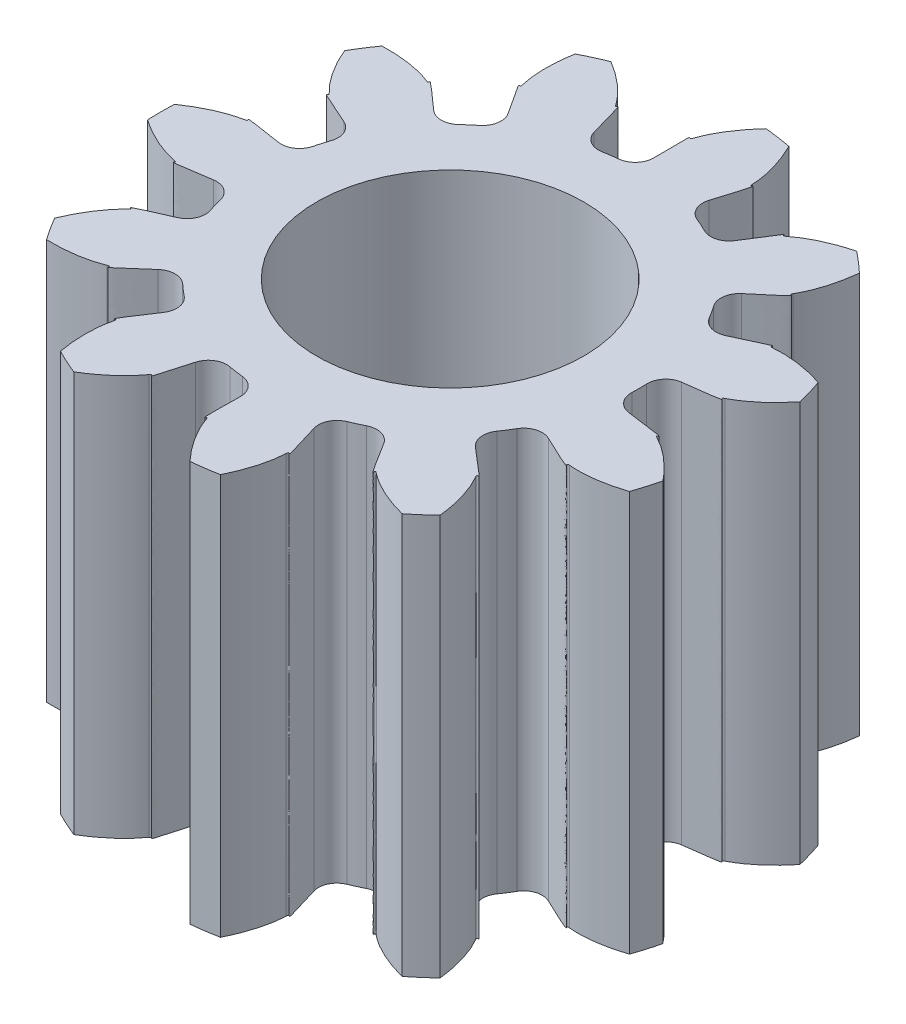
SolidWorks part; units mm, degrees
ref_plane "Front" through (0, 0, 0) normal (0, 0, 1) x (1, 0, 0)
ref_plane "Top" through (0, 0, 0) normal (0, 1, 0) x (1, 0, 0)
ref_plane "Right" through (0, 0, 0) normal (1, 0, 0) x (0, 0, -1)
ref_plane "Plane1" through (0, -4.5, 0) normal (0, -1, 0) x (1, 0, 0)
sketch "Sketch1" plane through (0, -4.5, 0) normal (0, -1, 0) x (1, 0, 0)
  line L0 (-2.1271, 0.9333) -> (-1.9459, 0.8539)
  line L1 (-2.0986, 0.3337) -> (-2.294, 0.3649)
  line L2 (-2.294, -0.3649) -> (-2.0986, -0.3337)
  line L3 (-1.9459, -0.8539) -> (-2.1271, -0.9333)
  line L4 (-1.7326, -1.5472) -> (-1.585, -1.4154)
  line L5 (-1.1754, -1.7703) -> (-1.2849, -1.9352)
  line L6 (-0.6211, -2.2383) -> (-0.5682, -2.0476)
  line L7 (-0.0317, -2.1248) -> (-0.0347, -2.3226)
  line L8 (0.6877, -2.2188) -> (0.629, -2.0298)
  line L9 (1.1221, -1.8046) -> (1.2265, -1.9727)
  line L10 (1.778, -1.4948) -> (1.6265, -1.3675)
  line L11 (1.9196, -0.9115) -> (2.0983, -0.9964)
  line L12 (2.3039, -0.2962) -> (2.1076, -0.271)
  line L13 (2.1076, 0.271) -> (2.3039, 0.2962)
  line L14 (2.0983, 0.9964) -> (1.9196, 0.9115)
  line L15 (1.6265, 1.3675) -> (1.778, 1.4948)
  line L16 (1.2265, 1.9727) -> (1.1221, 1.8046)
  line L17 (0.629, 2.0298) -> (0.6877, 2.2188)
  line L18 (-0.0347, 2.3226) -> (-0.0317, 2.1248)
  line L19 (-0.5682, 2.0476) -> (-0.6211, 2.2383)
  line L20 (-1.2849, 1.9352) -> (-1.1754, 1.7703)
  line L21 (-1.585, 1.4154) -> (-1.7326, 1.5472)
  arc A0 (-1.9459, 0.8539) -> (-2.0986, 0.3337) centre (0, 0) ccw
  arc A1 (-3.2465, 0.1513) -> (-3.2465, -0.1513) centre (0, 0) ccw
  arc A2 (-2.0986, -0.3337) -> (-1.9459, -0.8539) centre (0, 0) ccw
  arc A3 (-2.8129, -1.6279) -> (-2.6493, -1.8825) centre (0, 0) ccw
  arc A4 (-1.585, -1.4154) -> (-1.1754, -1.7703) centre (0, 0) ccw
  arc A5 (-1.4863, -2.8902) -> (-1.211, -3.016) centre (0, 0) ccw
  arc A6 (-0.5682, -2.0476) -> (-0.0317, -2.1248) centre (0, 0) ccw
  arc A7 (0.3122, -3.235) -> (0.6118, -3.1919) centre (0, 0) ccw
  arc A8 (0.629, -2.0298) -> (1.1221, -1.8046) centre (0, 0) ccw
  arc A9 (2.0116, -2.5526) -> (2.2404, -2.3544) centre (0, 0) ccw
  arc A10 (1.6265, -1.3675) -> (1.9196, -0.9115) centre (0, 0) ccw
  arc A11 (3.0723, -1.0598) -> (3.1576, -0.7694) centre (0, 0) ccw
  arc A12 (2.1076, -0.271) -> (2.1076, 0.271) centre (0, 0) ccw
  arc A13 (3.1576, 0.7694) -> (3.0723, 1.0598) centre (0, 0) ccw
  arc A14 (1.9196, 0.9115) -> (1.6265, 1.3675) centre (0, 0) ccw
  arc A15 (2.2404, 2.3544) -> (2.0116, 2.5526) centre (0, 0) ccw
  arc A16 (1.1221, 1.8046) -> (0.629, 2.0298) centre (0, 0) ccw
  arc A17 (0.6118, 3.1919) -> (0.3122, 3.235) centre (0, 0) ccw
  arc A18 (-0.0317, 2.1248) -> (-0.5682, 2.0476) centre (0, 0) ccw
  arc A19 (-1.211, 3.016) -> (-1.4863, 2.8902) centre (0, 0) ccw
  arc A20 (-1.1754, 1.7703) -> (-1.585, 1.4154) centre (0, 0) ccw
  arc A21 (-2.6493, 1.8825) -> (-2.8129, 1.6279) centre (0, 0) ccw
  ellipse E0 centre (-3.0578, -0.4226) end of major axis (-2.2508, 0.2924) minor radius 0.5689 (-2.7016, 0.3954) -> (-3.2465, 0.1513) ccw
  ellipse E1 centre (-3.0578, 0.4226) end of major axis (-2.2508, -0.2924) minor radius 0.5689 (-3.2465, -0.1513) -> (-2.7016, -0.3954) ccw
  ellipse E2 centre (-2.3439, -2.0087) end of major axis (-2.6362, -3.0465) minor radius 0.5689 (-2.4865, -1.128) -> (-2.8129, -1.6279) ccw
  ellipse E3 centre (-2.8009, -1.2977) end of major axis (-1.7354, -1.4629) minor radius 0.5689 (-2.6493, -1.8825) -> (-2.059, -1.7932) ccw
  ellipse E4 centre (-0.8858, -2.957) end of major axis (-1.201, -1.9259) minor radius 0.5689 (-1.482, -2.2932) -> (-1.4863, -2.8902) ccw
  ellipse E5 centre (-1.6547, -2.6059) end of major axis (-2.6404, -3.043) minor radius 0.5689 (-1.211, -3.016) -> (-0.7626, -2.6217) ccw
  ellipse E6 centre (0.8535, -2.9665) end of major axis (0.0309, -2.2695) minor radius 0.5689 (-0.0069, -2.7304) -> (0.3122, -3.235) ccw
  ellipse E7 centre (0.0169, -3.0868) end of major axis (-0.5761, -3.9874) minor radius 0.5689 (0.6118, -3.1919) -> (0.7758, -2.6178) ccw
  ellipse E8 centre (2.3218, -2.0342) end of major axis (3.3907, -2.1758) minor radius 0.5689 (1.4704, -2.3007) -> (2.0116, -2.5526) ccw
  ellipse E9 centre (1.6831, -2.5877) end of major axis (1.695, -1.5095) minor radius 0.5689 (2.2404, -2.3544) -> (2.068, -1.7828) ccw
  ellipse E10 centre (3.053, -0.456) end of major axis (4.0288, 0.0027) minor radius 0.5689 (2.4808, -1.1405) -> (3.0723, -1.0598) ccw
  ellipse E11 centre (2.8149, -1.267) end of major axis (2.242, -0.3535) minor radius 0.5689 (3.1576, -0.7694) -> (2.7036, -0.3818) ccw
  ellipse E12 centre (2.8149, 1.267) end of major axis (2.242, 0.3535) minor radius 0.5689 (2.7036, 0.3818) -> (3.1576, 0.7694) ccw
  ellipse E13 centre (3.053, 0.456) end of major axis (4.0288, -0.0027) minor radius 0.5689 (3.0723, 1.0598) -> (2.4808, 1.1405) ccw
  ellipse E14 centre (1.6831, 2.5877) end of major axis (1.695, 1.5095) minor radius 0.5689 (2.068, 1.7828) -> (2.2404, 2.3544) ccw
  ellipse E15 centre (2.3218, 2.0342) end of major axis (3.3907, 2.1758) minor radius 0.5689 (2.0116, 2.5526) -> (1.4704, 2.3007) ccw
  ellipse E16 centre (0.0169, 3.0868) end of major axis (0.6098, 2.1863) minor radius 0.5689 (0.7758, 2.6178) -> (0.6118, 3.1919) ccw
  ellipse E17 centre (0.8535, 2.9665) end of major axis (1.6761, 3.6636) minor radius 0.5689 (0.3122, 3.235) -> (-0.0069, 2.7304) ccw
  ellipse E18 centre (-1.6547, 2.6059) end of major axis (-0.669, 2.1689) minor radius 0.5689 (-0.7626, 2.6217) -> (-1.211, 3.016) ccw
  ellipse E19 centre (-0.8858, 2.957) end of major axis (-0.5707, 3.9882) minor radius 0.5689 (-1.4863, 2.8902) -> (-1.482, 2.2932) ccw
  ellipse E20 centre (-2.8009, 1.2977) end of major axis (-1.7354, 1.4629) minor radius 0.5689 (-2.059, 1.7932) -> (-2.6493, 1.8825) ccw
  ellipse E21 centre (-2.3439, 2.0087) end of major axis (-2.6362, 3.0465) minor radius 0.5689 (-2.8129, 1.6279) -> (-2.4865, 1.128) ccw
  spline S0 degree 3 poles (-2.294, 0.3649) (-2.8728, 0.4571) (-2.6163, 0.4112) (-2.7016, 0.3954) knots 0 0 0 0 1 1 1 1
  spline S1 degree 3 poles (-2.294, -0.3649) (-2.8728, -0.4571) (-2.6163, -0.4112) (-2.7016, -0.3954) knots 0 0 0 0 1 1 1 1
  spline S2 degree 3 poles (-2.1271, -0.9333) (-2.6639, -1.1686) (-2.4233, -1.0686) (-2.4865, -1.128) knots 0 0 0 0 1 1 1 1
  spline S3 degree 3 poles (-1.7326, -1.5472) (-2.1696, -1.9377) (-1.9787, -1.7604) (-2.059, -1.7932) knots 0 0 0 0 1 1 1 1
  spline S4 degree 3 poles (-1.2849, -1.9352) (-1.6093, -2.4233) (-1.4609, -2.2091) (-1.482, -2.2932) knots 0 0 0 0 1 1 1 1
  spline S5 degree 3 poles (-0.6211, -2.2383) (-0.7776, -2.8031) (-0.7128, -2.5507) (-0.7626, -2.6217) knots 0 0 0 0 1 1 1 1
  spline S6 degree 3 poles (-0.0347, -2.3226) (-0.0437, -2.9086) (-0.0347, -2.6482) (-0.0069, -2.7304) knots 0 0 0 0 1 1 1 1
  spline S7 degree 3 poles (0.6877, -2.2188) (0.8613, -2.7785) (0.7794, -2.5312) (0.7758, -2.6178) knots 0 0 0 0 1 1 1 1
  spline S8 degree 3 poles (1.2265, -1.9727) (1.5358, -2.4705) (1.4026, -2.2466) (1.4704, -2.3007) knots 0 0 0 0 1 1 1 1
  spline S9 degree 3 poles (1.778, -1.4948) (2.2268, -1.8718) (2.0241, -1.708) (2.068, -1.7828) knots 0 0 0 0 1 1 1 1
  spline S10 degree 3 poles (2.0983, -0.9964) (2.6277, -1.248) (2.3945, -1.1317) (2.4808, -1.1405) knots 0 0 0 0 1 1 1 1
  spline S11 degree 3 poles (2.3039, -0.2962) (2.8853, -0.3707) (2.6262, -0.3425) (2.7036, -0.3818) knots 0 0 0 0 1 1 1 1
  spline S12 degree 3 poles (2.3039, 0.2962) (2.8853, 0.3707) (2.6262, 0.3425) (2.7036, 0.3818) knots 0 0 0 0 1 1 1 1
  spline S13 degree 3 poles (2.0983, 0.9964) (2.6277, 1.248) (2.3945, 1.1317) (2.4808, 1.1405) knots 0 0 0 0 1 1 1 1
  spline S14 degree 3 poles (1.778, 1.4948) (2.2268, 1.8718) (2.0241, 1.708) (2.068, 1.7828) knots 0 0 0 0 1 1 1 1
  spline S15 degree 3 poles (1.2265, 1.9727) (1.5358, 2.4705) (1.4026, 2.2466) (1.4704, 2.3007) knots 0 0 0 0 1 1 1 1
  spline S16 degree 3 poles (0.6877, 2.2188) (0.8613, 2.7785) (0.7794, 2.5312) (0.7758, 2.6178) knots 0 0 0 0 1 1 1 1
  spline S17 degree 3 poles (-0.0347, 2.3226) (-0.0437, 2.9086) (-0.0347, 2.6482) (-0.0069, 2.7304) knots 0 0 0 0 1 1 1 1
  spline S18 degree 3 poles (-0.6211, 2.2383) (-0.7776, 2.8031) (-0.7128, 2.5507) (-0.7626, 2.6217) knots 0 0 0 0 1 1 1 1
  spline S19 degree 3 poles (-1.2849, 1.9352) (-1.6093, 2.4233) (-1.4609, 2.2091) (-1.482, 2.2932) knots 0 0 0 0 1 1 1 1
  spline S20 degree 3 poles (-1.7326, 1.5472) (-2.1696, 1.9377) (-1.9787, 1.7604) (-2.059, 1.7932) knots 0 0 0 0 1 1 1 1
  spline S21 degree 3 poles (-2.1271, 0.9333) (-2.6639, 1.1686) (-2.4233, 1.0686) (-2.4865, 1.128) knots 0 0 0 0 1 1 1 1
  point P6 (-3.0578, -0.4226)
  point P7 (-2.2508, 0.2924)
  point P8 (-2.6806, -0.8484)
  point P9 (-2.7016, 0.3954)
  point P10 (-3.2465, 0.1513)
  point P11 (-2.9858, 0.3014)
  point P12 (-3.1298, -1.1466)
  point P20 (-3.0578, 0.4226)
  point P21 (-2.2508, -0.2924)
  point P22 (-2.6806, 0.8484)
  point P23 (-3.2465, -0.1513)
  point P24 (-2.7016, -0.3954)
  point P25 (-2.9858, -0.3014)
  point P26 (-3.1298, 1.1466)
  point P38 (-2.3439, -2.0087)
  point P39 (-1.7963, -2.1629)
  point P40 (-2.6362, -3.0465)
  point P41 (-2.4865, -1.128)
  point P42 (-2.8129, -1.6279)
  point P43 (-2.6748, -1.3607)
  point P44 (-2.013, -2.6567)
  point P52 (-2.8009, -1.2977)
  point P53 (-1.7354, -1.4629)
  point P54 (-2.7137, -0.7355)
  point P55 (-2.6493, -1.8825)
  point P56 (-2.059, -1.7932)
  point P57 (-2.3489, -1.8679)
  point P58 (-3.2529, -0.7274)
  point P70 (-0.8858, -2.957)
  point P71 (-0.3418, -2.7908)
  point P72 (-0.5707, -3.9882)
  point P73 (-1.482, -2.2932)
  point P74 (-1.4863, -2.8902)
  point P75 (-1.5146, -2.5908)
  point P76 (-0.2571, -3.3233)
  point P84 (-1.6547, -2.6059)
  point P85 (-0.669, -2.1689)
  point P86 (-1.8853, -2.0859)
  point P87 (-1.211, -3.016)
  point P88 (-0.7626, -2.6217)
  point P89 (-0.9662, -2.8413)
  point P90 (-2.3432, -2.3706)
  point P102 (0.8535, -2.9665)
  point P103 (1.6761, -3.6636)
  point P104 (0.4857, -3.4006)
  point P105 (-0.0069, -2.7304)
  point P106 (0.3122, -3.235)
  point P107 (0.1266, -2.9984)
  point P108 (1.5804, -2.9347)
  point P116 (0.0169, -3.0868)
  point P117 (0.492, -3.3997)
  point P118 (0.6098, -2.1863)
  point P119 (0.6118, -3.1919)
  point P120 (0.7758, -2.6178)
  point P121 (0.7233, -2.9126)
  point P122 (-0.6896, -3.2611)
  point P134 (2.3218, -2.0342)
  point P135 (3.3907, -2.1758)
  point P136 (2.2471, -2.5981)
  point P137 (1.4704, -2.3007)
  point P138 (2.0116, -2.5526)
  point P139 (1.7275, -2.454)
  point P140 (2.9162, -1.6144)
  point P148 (1.6831, -2.5877)
  point P149 (2.2519, -2.594)
  point P150 (1.695, -1.5095)
  point P151 (2.2404, -2.3544)
  point P152 (2.068, -1.7828)
  point P153 (2.1831, -2.0592)
  point P154 (1.183, -3.1162)
  point P166 (3.053, -0.456)
  point P167 (4.0288, 0.0027)
  point P168 (3.295, -0.9708)
  point P169 (2.4808, -1.1405)
  point P170 (3.0723, -1.0598)
  point P171 (2.78, -1.1304)
  point P172 (3.326, 0.2185)
  point P180 (2.8149, -1.267)
  point P181 (3.2968, -0.9647)
  point P182 (2.242, -0.3535)
  point P183 (3.1576, -0.7694)
  point P184 (2.7036, -0.3818)
  point P185 (2.9498, -0.552)
  point P186 (2.6799, -1.982)
  point P198 (2.8149, 1.267)
  point P199 (3.2968, 0.9647)
  point P200 (2.242, 0.3535)
  point P201 (2.7036, 0.3818)
  point P202 (3.1576, 0.7694)
  point P203 (2.9498, 0.552)
  point P204 (2.6799, 1.982)
  point P212 (3.053, 0.456)
  point P213 (4.0288, -0.0027)
  point P214 (3.295, 0.9708)
  point P215 (3.0723, 1.0598)
  point P216 (2.4808, 1.1405)
  point P217 (2.78, 1.1304)
  point P218 (3.326, -0.2185)
  point P230 (1.6831, 2.5877)
  point P231 (2.2519, 2.594)
  point P232 (1.695, 1.5095)
  point P233 (2.068, 1.7828)
  point P234 (2.2404, 2.3544)
  point P235 (2.1831, 2.0592)
  point P236 (1.183, 3.1162)
  point P244 (2.3218, 2.0342)
  point P245 (3.3907, 2.1758)
  point P246 (2.2471, 2.5981)
  point P247 (2.0116, 2.5526)
  point P248 (1.4704, 2.3007)
  point P249 (1.7275, 2.454)
  point P250 (2.9162, 1.6144)
  point P262 (0.0169, 3.0868)
  point P263 (0.492, 3.3997)
  point P264 (0.6098, 2.1863)
  point P265 (0.7758, 2.6178)
  point P266 (0.6118, 3.1919)
  point P267 (0.7233, 2.9126)
  point P268 (-0.6896, 3.2611)
  point P276 (0.8535, 2.9665)
  point P277 (1.6761, 3.6636)
  point P278 (0.4857, 3.4006)
  point P279 (0.3122, 3.235)
  point P280 (-0.0069, 2.7304)
  point P281 (0.1266, 2.9984)
  point P282 (1.5804, 2.9347)
  point P294 (-1.6547, 2.6059)
  point P295 (-0.669, 2.1689)
  point P296 (-1.8853, 2.0859)
  point P297 (-0.7626, 2.6217)
  point P298 (-1.211, 3.016)
  point P299 (-0.9662, 2.8413)
  point P300 (-2.3432, 2.3706)
  point P308 (-0.8858, 2.957)
  point P309 (-0.3418, 2.7908)
  point P310 (-0.5707, 3.9882)
  point P311 (-1.4863, 2.8902)
  point P312 (-1.482, 2.2932)
  point P313 (-1.5146, 2.5908)
  point P314 (-0.2571, 3.3233)
  point P326 (-2.8009, 1.2977)
  point P327 (-1.7354, 1.4629)
  point P328 (-2.7137, 0.7355)
  point P329 (-2.059, 1.7932)
  point P330 (-2.6493, 1.8825)
  point P331 (-2.3489, 1.8679)
  point P332 (-3.2529, 0.7274)
  point P340 (-2.3439, 2.0087)
  point P341 (-1.7963, 2.1629)
  point P342 (-2.6362, 3.0465)
  point P343 (-2.8129, 1.6279)
  point P344 (-2.4865, 1.128)
  point P345 (-2.6748, 1.3607)
  point P346 (-2.013, 2.6567)
extrude "Boss-Extrude1" add sketch "Sketch1" against normal blind 4.5
hole_wizard "Ø3.0 (3) Diameter Hole1" positions "Sketch3" profile "Sketch2" hole size "Ø3.0" standard "ANSI Metric"
sketch "Sketch3" plane through (0, -4.5, 0) normal (0, -1, 0) x (-1, 0, 0)
  point P0 (0, 0)
sketch "Sketch2" plane through (0, -4.5, 0) normal (1, 0, 0) x (0, 0, -1)
  line L0 (0, 0) -> (0, 4.5)
  line L1 (0, 4.5) -> (1.5, 4.5)
  line L2 (1.5, 4.5) -> (1.5, 0)
  line L5 (1.5, 0) -> (0, 0)
  line L11 (0, -6.35) -> (0, 107.95) construction
  dimension "Thru Hole Dia." = 3
  dimension "Thru Hole Depth" = 4.5
fillet "Fillet1" radius 0.207 22 edges at (-1.1754, -2.25, -1.7703) (-0.0317, -2.25, -2.1248) (-1.9459, -2.25, -0.8539) (-1.585, -2.25, 1.4154) (-0.5682, -2.25, -2.0476) (-1.9459, -2.25, 0.8539) (-1.585, -2.25, -1.4154) (1.9196, -2.25, -0.9115) (-2.0986, -2.25, -0.3337) (2.1076, -2.25, -0.271) (1.1221, -2.25, 1.8046) (1.6265, -2.25, -1.3675) (0.629, -2.25, 2.0298) (2.1076, -2.25, 0.271) (-0.0317, -2.25, 2.1248) (1.1221, -2.25, -1.8046) (-0.5682, -2.25, 2.0476) (1.9196, -2.25, 0.9115) (-1.1754, -2.25, 1.7703) (0.629, -2.25, -2.0298) (1.6265, -2.25, 1.3675) (-2.0986, -2.25, 0.3337) tangent propagation no
